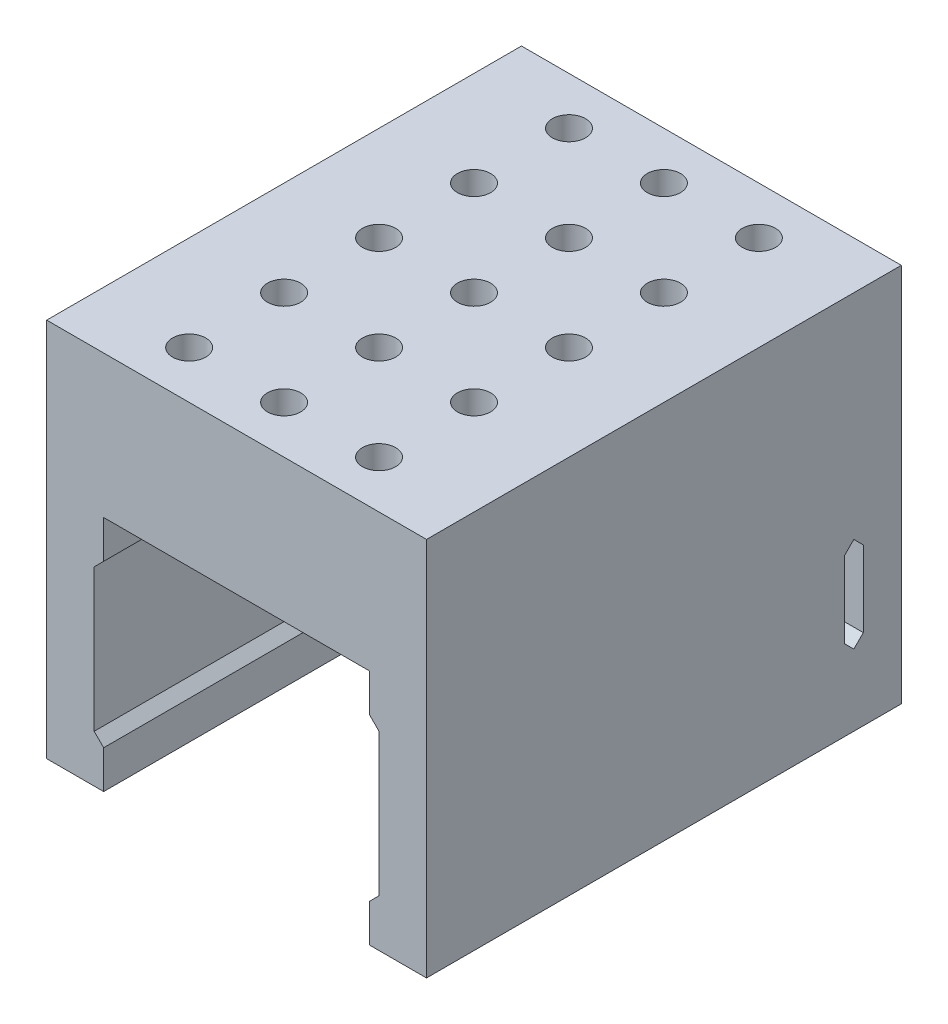
SolidWorks part; units mm, degrees
ref_plane "正面" through (0, 0, 0) normal (0, 0, 1) x (1, 0, 0)
ref_plane "平面" through (0, 0, 0) normal (0, 1, 0) x (1, 0, 0)
ref_plane "右側面" through (0, 0, 0) normal (1, 0, 0) x (0, 0, -1)
sketch "ｽｹｯﾁ1" plane through (0, 0, 0) normal (0, 0, 1) x (1, 0, 0)
  line L0 (20, 0) -> (20, 5) construction
  line L1 (0, 0) -> (40, 0)
  line L2 (0, 0) -> (0, 40)
  line L3 (0, 40) -> (40, 40)
  line L4 (40, 0) -> (40, 40)
  line L5 (5, 5) -> (35, 5)
  line L6 (5, 5) -> (5, 20)
  line L7 (5, 20) -> (35, 20)
  line L8 (35, 5) -> (35, 20)
  dimension "D1" = 30
  dimension "D2" = 15
  dimension "D3" = 5
  dimension "D4" = 5
  dimension "D5" = 40
extrude "ﾎﾞｽ - 押し出し1" add sketch "ｽｹｯﾁ1" along normal blind 50
sketch "ｽｹｯﾁ3" plane through (0, 0, 0) normal (0, 0, -1) x (-1, 0, 0)
  line L0 (-35, 12.5) -> (-5, 12.5) construction
  line L2 (-35, 5) -> (-35, 20) construction
  line L8 (-6, 25) -> (-34, 25)
  line L9 (-5, 20) -> (-5, 5) construction
  line L10 (-6, 25) -> (-6, 0)
  line L11 (-6, 0) -> (-34, 0)
  line L12 (-34, 25) -> (-34, 0)
  line L13 (-6, 25) -> (-34, 0) construction
  line L14 (-6, 0) -> (-34, 25) construction
  line L15 (0, 0) -> (-40, 0) construction
  point P4 (-20, 12.5)
  dimension "D1" = 1
extrude "ｶｯﾄ - 押し出し1" cut sketch "ｽｹｯﾁ3" against normal up to next
chamfer "面取り1" distance 1 angle 45 4 edges at (6, 20, 25) (6, 5, 25) (34, 5, 25) (34, 20, 25)
sketch "ｽｹｯﾁ4" plane through (0, 40, 0) normal (0, 1, 0) x (1, 0, 0)
  line L0 (0, -5) -> (10, -5) construction
  line L1 (0, -50) -> (0, 0) construction
  line L2 (40, 0) -> (0, 0) construction
  circle A0 centre (10, -5) radius 1.75
  circle A1 centre (20, -5) radius 1.75
  circle A2 centre (30, -5) radius 1.75
  circle A3 centre (10, -15) radius 1.75
  circle A4 centre (20, -15) radius 1.75
  circle A5 centre (30, -15) radius 1.75
  circle A6 centre (10, -25) radius 1.75
  circle A7 centre (20, -25) radius 1.75
  circle A8 centre (30, -25) radius 1.75
  circle A9 centre (10, -35) radius 1.75
  circle A10 centre (20, -35) radius 1.75
  circle A11 centre (30, -35) radius 1.75
  circle A12 centre (10, -45) radius 1.75
  circle A13 centre (20, -45) radius 1.75
  circle A14 centre (30, -45) radius 1.75
  dimension "D3" = 3.5
  dimension "D1" = 5
  dimension "D2" = 10
  dimension "D4" = 3
  dimension "D5" = 5
extrude "ｶｯﾄ - 押し出し2" cut sketch "ｽｹｯﾁ4" against normal up to next
sketch "ｽｹｯﾁ5" plane through (40, 0, 0) normal (1, 0, 0) x (0, 0, -1)
  line L0 (-5, 0) -> (-5, 12.5) construction
  line L1 (-50, 0) -> (0, 0) construction
  line L2 (0, 0) -> (0, 40) construction
  line L4 (-4, 7.5) -> (-6, 7.5)
  line L5 (-4, 7.5) -> (-4, 17.5)
  line L6 (-4, 17.5) -> (-6, 17.5)
  line L7 (-6, 7.5) -> (-6, 17.5)
  line L8 (-4, 7.5) -> (-6, 17.5) construction
  line L9 (-4, 17.5) -> (-6, 7.5) construction
  dimension "D1" = 5
  dimension "D2" = 2
  dimension "D3" = 10
  dimension "D4" = 12.5
extrude "ｶｯﾄ - 押し出し4" cut sketch "ｽｹｯﾁ5" against normal through all
chamfer "面取り3" distance 1 angle 45 8 edges at (2.5, 17.5, 6) (2.5, 17.5, 4) (2.5, 7.5, 4) (2.5, 7.5, 6) (37.5, 7.5, 4) (37.5, 7.5, 6) (37.5, 17.5, 4) (37.5, 17.5, 6)
